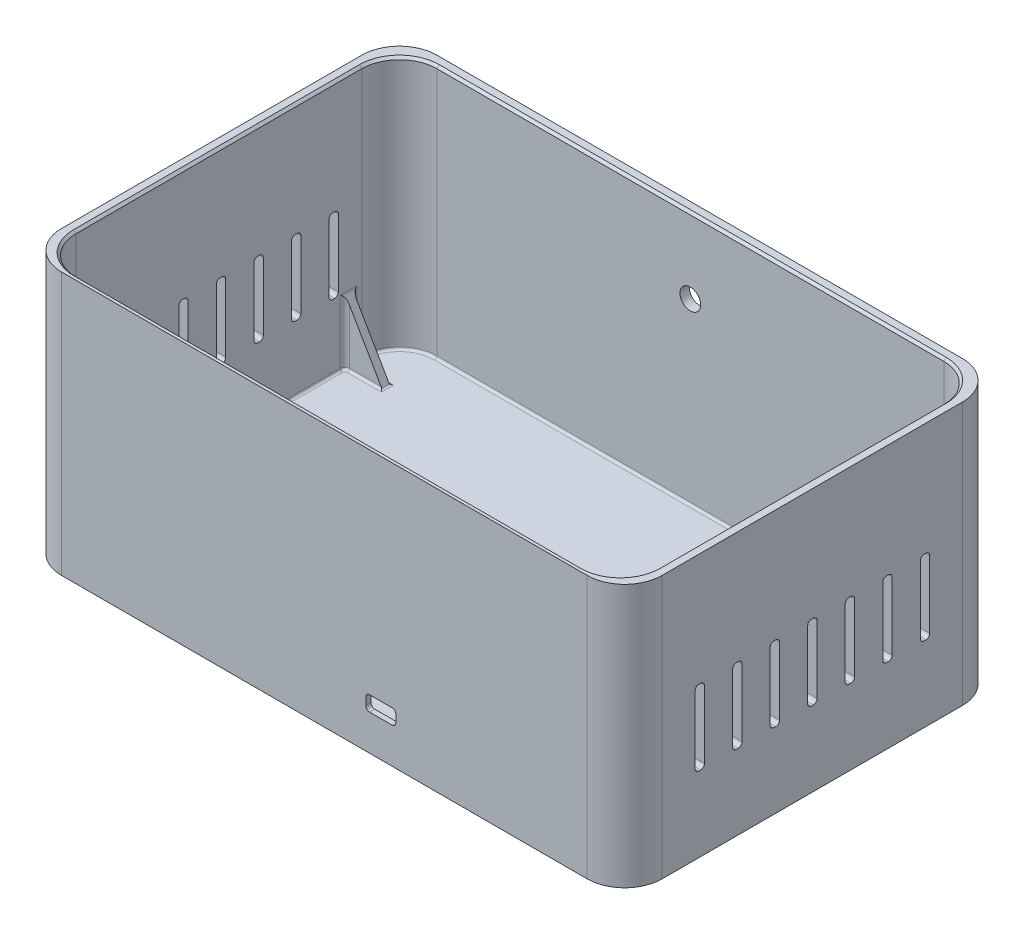
SolidWorks part; units mm, degrees
ref_plane "Front Plane" through (0, 0, 0) normal (0, 0, 1) x (1, 0, 0)
ref_plane "Top Plane" through (0, 0, 0) normal (0, 1, 0) x (1, 0, 0)
ref_plane "Right Plane" through (0, 0, 0) normal (1, 0, 0) x (0, 0, -1)
sketch "Sketch1" plane through (0, 0, 0) normal (0, 1, 0) x (1, 0, 0)
  line L1 (-101.6, -63.5) -> (101.6, -63.5)
  line L2 (-101.6, -63.5) -> (-101.6, 63.5)
  line L3 (-101.6, 63.5) -> (101.6, 63.5)
  line L4 (101.6, -63.5) -> (101.6, 63.5)
  line L5 (-101.6, -63.5) -> (101.6, 63.5) construction
  line L6 (-101.6, 63.5) -> (101.6, -63.5) construction
  point P0 (0, 0)
  dimension "D1" = 203.2
  dimension "D2" = 127
extrude "Boss-Extrude1" add sketch "Sketch1" along normal blind 88.9
shell "Shell1" thickness 3.175
fillet "Fillet3" radius 12.7 8 edges at (101.6, 44.45, -63.5) (101.6, 44.45, 63.5) (-101.6, 44.45, 63.5) (-101.6, 44.45, -63.5) (98.425, 46.0375, -60.325) (98.425, 46.0375, 61.75) (-98.425, 46.0375, 61.75) (-98.425, 46.0375, -60.325)
chamfer "Chamfer2" distance 0.7937 angle 45 8 edges at (98.425, 88.9, 0.7125) (94.7053, 88.9, -56.6053) (94.7053, 88.9, 58.0303) (0, 88.9, -60.325) (0, 88.9, 61.75) (-94.7053, 88.9, -56.6053) (-94.7053, 88.9, 58.0303) (-98.425, 88.9, 0.7125)
sketch "Sketch2" plane through (0, 3.175, 0) normal (0, 1, 0) x (1, 0, 0)
  line L0 (-85.725, -61.75) -> (85.725, -61.75) construction
  line L1 (-63.7475, -61.75) -> (-51.3975, -61.75)
  line L2 (50.2525, -61.75) -> (62.6025, -61.75)
  circle A0 centre (56.4275, 5.25) radius 3.175
  circle A1 centre (-57.5725, 5.25) radius 3.175
  arc A4 (-60.7475, -58.75) -> (-63.7475, -61.75) centre (-63.7475, -58.75) cw
  arc A5 (-54.3975, -58.75) -> (-51.3975, -61.75) centre (-51.3975, -58.75) ccw
  arc A6 (-54.3975, -58.75) -> (-60.7475, -58.75) centre (-57.5725, -58.75) ccw
  arc A7 (53.2525, -58.75) -> (50.2525, -61.75) centre (50.2525, -58.75) cw
  arc A8 (59.6025, -58.75) -> (62.6025, -61.75) centre (62.6025, -58.75) ccw
  arc A9 (59.6025, -58.75) -> (53.2525, -58.75) centre (56.4275, -58.75) ccw
  point P22 (-57.5725, -58.75)
  point P23 (56.4275, -58.75)
  dimension "D1" = 6.35
  dimension "D6" = 3.175
  dimension "D7" = 3.175
  dimension "D2" = 114
  dimension "D3" = 64
  dimension "D4" = 57.5725
  dimension "D5" = 5.25
extrude "Boss-Extrude3" add sketch "Sketch2" along normal blind 6.35
sketch "Sketch3" plane through (0, 0, 63.5) normal (0, 0, 1) x (1, 0, 0)
  line L1 (15.29, 17.145) -> (22.95, 17.145)
  line L2 (14.04, 15.895) -> (14.04, 13.315)
  line L3 (15.29, 12.065) -> (22.95, 12.065)
  line L4 (24.2, 15.895) -> (24.2, 13.315)
  line L5 (14.04, 17.145) -> (24.2, 12.065) construction
  line L6 (14.04, 12.065) -> (24.2, 17.145) construction
  line L7 (-88.9, 0) -> (88.9, 0) construction
  arc A0 (22.95, 12.065) -> (24.2, 13.315) centre (22.95, 13.315) ccw
  arc A1 (24.2, 15.895) -> (22.95, 17.145) centre (22.95, 15.895) ccw
  arc A2 (15.29, 12.065) -> (14.04, 13.315) centre (15.29, 13.315) cw
  arc A3 (14.04, 15.895) -> (15.29, 17.145) centre (15.29, 15.895) cw
  point P0 (19.12, 14.605)
  dimension "D3" = 1.25
  dimension "D1" = 10.16
  dimension "D2" = 5.08
  dimension "D4" = 19.12
  dimension "D5" = 14.605
extrude "Cut-Extrude1" cut sketch "Sketch3" against normal up to vertex (1.75 mm away)
sketch "Sketch6" plane through (-101.6, 0, 0) normal (-1, 0, 0) x (0, 0, 1)
  line L1 (-38.4175, 50.8) -> (-37.7825, 50.8)
  line L2 (-39.6875, 49.53) -> (-39.6875, 26.67)
  line L3 (-38.4175, 25.4) -> (-37.7825, 25.4)
  line L4 (-36.5125, 49.53) -> (-36.5125, 26.67)
  line L5 (-39.6875, 50.8) -> (-36.5125, 25.4) construction
  line L6 (-39.6875, 25.4) -> (-36.5125, 50.8) construction
  arc A0 (-37.7825, 25.4) -> (-36.5125, 26.67) centre (-37.7825, 26.67) ccw
  arc A1 (-38.4175, 25.4) -> (-39.6875, 26.67) centre (-38.4175, 26.67) cw
  arc A2 (-36.5125, 49.53) -> (-37.7825, 50.8) centre (-37.7825, 49.53) ccw
  arc A3 (-39.6875, 49.53) -> (-38.4175, 50.8) centre (-38.4175, 49.53) cw
  point P0 (-38.1, 38.1)
  dimension "D2" = 1.27
  dimension "D1" = 38.1
  dimension "D3" = 38.1
  dimension "D4" = 3.175
  dimension "D5" = 25.4
extrude "Cut-Extrude4" cut sketch "Sketch6" against normal up to next
pattern_linear "LPattern1" count 7 spacing 12.7 along (0, 0, 1) of "Cut-Extrude4"
ref_plane "Plane1" through (0, 0, 43.18) normal (0, 0, 1) x (1, 0, 0)
sketch "Sketch8" plane through (0, 0, 43.18) normal (0, 0, 1) x (1, 0, 0)
  line L0 (98.425, 25.172) -> (85.725, 3.175)
  line L1 (98.425, 3.175) -> (98.425, 88.1062) construction
  line L2 (98.425, 3.175) -> (85.725, 3.175) construction
  line L3 (85.725, 3.175) -> (98.425, 3.175)
  line L4 (98.425, 3.175) -> (98.425, 25.172)
  line L5 (0, -48.895) -> (0, 48.895) construction
  line L6 (-98.425, 3.175) -> (-98.425, 25.172)
  line L7 (-85.725, 3.175) -> (-98.425, 3.175)
  line L8 (-98.425, 25.172) -> (-85.725, 3.175)
  dimension "D1" = 60
  dimension "D2" = 12.7
extrude "Boss-Extrude4" add sketch "Sketch8" along normal mid plane 2.54
mirror "Mirror2" about plane through (0, 0, 0) normal (0, 0, 1) of "Boss-Extrude4"
fillet "Fillet4" radius 0.7937 38 edges at (56.4275, 3.175, -8.425) (-57.5725, 3.175, -8.425) (-94.7053, 3.175, -56.6053) (0, 3.175, -60.325) (94.7053, 3.175, -56.6053) (98.425, 3.175, 46.75) (98.425, 3.175, -46.0375) (94.7053, 3.175, 58.0303) (74.1638, 3.175, 61.75) (60.4812, 3.175, 60.8713) (56.4275, 3.175, 55.575) (52.3738, 3.175, 60.8713) (-0.5725, 3.175, 61.75) (-53.5188, 3.175, 60.8713) (-57.5725, 3.175, 55.575) (-61.6262, 3.175, 60.8713) (-74.7362, 3.175, 61.75) (-94.7053, 3.175, 58.0303) (-98.425, 3.175, 46.75) (-98.425, 3.175, -46.0375) (98.425, 3.175, 0) (92.075, 3.175, -44.45) (85.725, 3.175, -43.18) (92.075, 3.175, -41.91) (92.075, 3.175, 41.91) (85.725, 3.175, 43.18) (92.075, 3.175, 44.45) (-92.075, 3.175, 44.45) (-85.725, 3.175, 43.18) (-92.075, 3.175, 41.91) (-98.425, 3.175, 0) (-92.075, 3.175, -41.91) (-85.725, 3.175, -43.18) (-92.075, 3.175, -44.45) (-98.425, 25.172, -43.18) (-98.425, 25.172, 43.18) (98.425, 25.172, 43.18) (98.425, 25.172, -43.18)
sketch "Sketch5" plane through (0, 9.525, 0) normal (0, 1, 0) x (1, 0, 0)
  circle A0 centre (-57.5725, 5.25) radius 1.575
  circle A1 centre (56.4275, 5.25) radius 1.575
  circle A2 centre (56.4275, -58.75) radius 1.575
  circle A3 centre (-57.5725, -58.75) radius 1.575
  dimension "D1" = 3.15
extrude "Cut-Extrude3" cut sketch "Sketch5" against normal blind 5
mirror "Mirror1" about plane through (0, 0, 0) normal (1, 0, 0) of "LPattern1", "Cut-Extrude4"
sketch "Sketch7" plane through (0, 0, -63.5) normal (0, 0, -1) x (-1, 0, 0)
  circle A0 centre (0, 63.5) radius 3.5
  dimension "D1" = 7
  dimension "D2" = 0
  dimension "D3" = 63.5
extrude "Cut-Extrude5" cut sketch "Sketch7" against normal up to next
fillet "Fillet5" radius 1.5875 16 edges at (98.1925, 3.4075, -41.6775) (98.1925, 3.4075, -44.6825) (98.1925, 3.4075, 41.6775) (98.1925, 3.4075, 44.6825) (-98.1925, 3.4075, -41.6775) (-98.1925, 3.4075, -44.6825) (-98.1925, 3.4075, 41.6775) (-98.1925, 3.4075, 44.6825) (-98.425, 14.6767, 44.45) (-98.425, 14.6767, 41.91) (-98.425, 14.6767, -44.45) (-98.425, 14.6767, -41.91) (98.425, 14.6767, 44.45) (98.425, 14.6767, 41.91) (98.425, 14.6767, -44.45) (98.425, 14.6767, -41.91)
